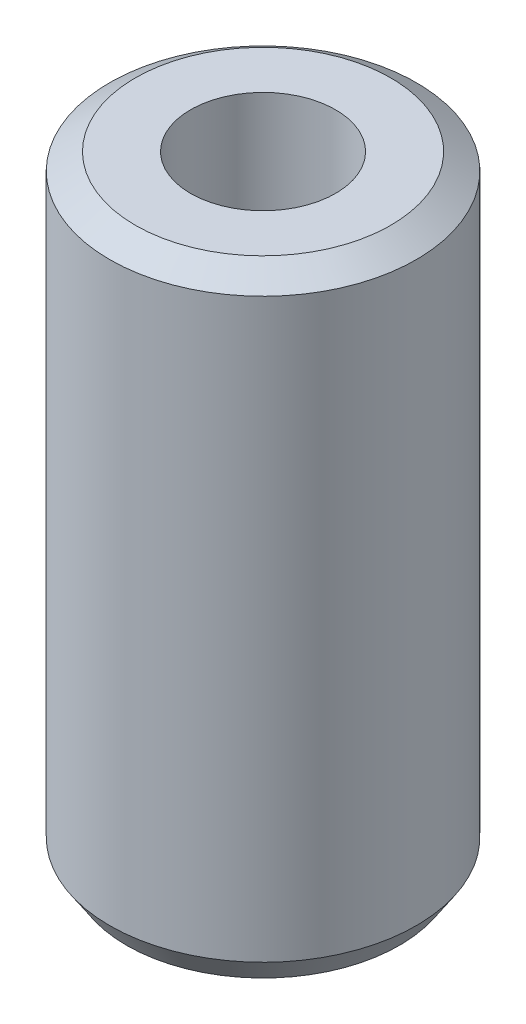
SolidWorks part; units mm, degrees
ref_plane "Front Plane" through (0, 0, 0) normal (0, 0, 1) x (1, 0, 0)
ref_plane "Top Plane" through (0, 0, 0) normal (0, 1, 0) x (1, 0, 0)
ref_plane "Right Plane" through (0, 0, 0) normal (1, 0, 0) x (0, 0, -1)
sketch "Sketch1" plane through (0, 0, 0) normal (0, 1, 0) x (1, 0, 0)
  circle A0 centre (0, 0) radius 42.5
  dimension "SHAFT_OD" = 85
extrude "Boss-Extrude1" add sketch "Sketch1" along normal blind 171.6817
sketch "Sketch2" plane through (0, 0, 0) normal (0, 1, 0) x (1, 0, 0)
  circle A0 centre (0, 0) radius 20.1031
  dimension "BORE_D" = 40.2063
extrude "Cut-Extrude1" cut sketch "Sketch2" along normal through all
chamfer "Chamfer1" distance 4.69 angle 56.547 2 edges at (0, 171.6817, 42.5) (0, 0, 42.5) first distance on face at (0, 171.6817, 42.5) first distance on face at (0, 0, 20.1031)
